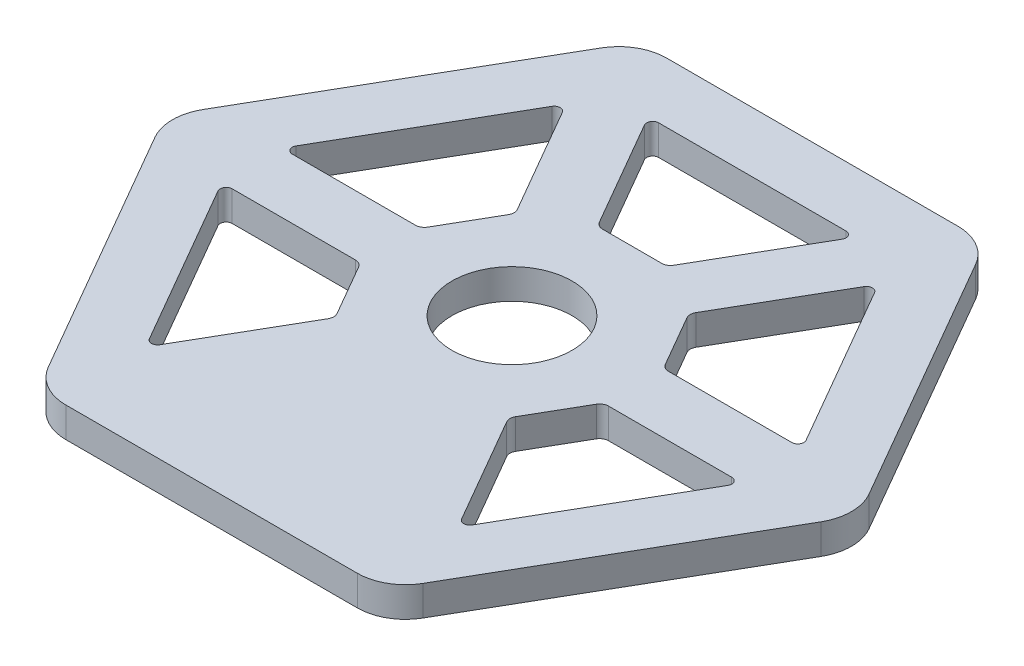
SolidWorks part; units mm, degrees
ref_plane "Front Plane" through (0, 0, 0) normal (0, 0, 1) x (1, 0, 0)
ref_plane "Top Plane" through (0, 0, 0) normal (0, 1, 0) x (1, 0, 0)
ref_plane "Right Plane" through (0, 0, 0) normal (1, 0, 0) x (0, 0, -1)
sketch "Sketch1" plane through (0, 0, 0) normal (0, 1, 0) x (1, 0, 0)
  line L1 (-57.735, 0) -> (-28.8675, -50)
  line L2 (-28.8675, -50) -> (28.8675, -50)
  line L3 (28.8675, -50) -> (57.735, 0)
  line L4 (57.735, 0) -> (28.8675, 50)
  line L5 (28.8675, 50) -> (-28.8675, 50)
  line L6 (-28.8675, 50) -> (-57.735, 0)
  circle A0 centre (0, 0) radius 50 construction
  circle A1 centre (0, 0) radius 50 construction
  dimension "D2" = 100
  dimension "D1" = 100
extrude "Boss-Extrude1" add sketch "Sketch1" along normal blind 5
fillet "Fillet1" radius 8 6 edges at (28.8675, 2.5, -50) (57.735, 2.5, 0) (28.8675, 2.5, 50) (-28.8675, 2.5, 50) (-57.735, 2.5, 0) (-28.8675, 2.5, -50)
sketch "Sketch2" plane through (0, 5, 0) normal (0, 1, 0) x (1, 0, 0)
  line L0 (0, 30) -> (0, 20) construction
  line L1 (0, 40) -> (0, 50) construction
  line L2 (6.2065, 20.75) -> (16.4545, 38.5)
  line L3 (15.5885, 40) -> (-15.5885, 40)
  line L4 (-16.4545, 38.5) -> (-6.2065, 20.75)
  line L5 (24.2487, 50) -> (-24.2487, 50) construction
  line L36 (4.9075, 20) -> (-4.9075, 20)
  line L37 (21.0733, 5) -> (41.5692, 5)
  line L38 (42.4352, 6.5) -> (26.8468, 33.5)
  line L39 (25.1147, 33.5) -> (14.8668, 15.75)
  line L40 (19.7742, 5.75) -> (14.8668, 14.25)
  line L41 (14.8668, -15.75) -> (25.1147, -33.5)
  line L42 (26.8468, -33.5) -> (42.4352, -6.5)
  line L43 (41.5692, -5) -> (21.0733, -5)
  line L44 (14.8668, -14.25) -> (19.7742, -5.75)
  line L45 (-6.2065, -20.75) -> (-16.4545, -38.5) construction
  line L46 (-15.5885, -40) -> (15.5885, -40) construction
  line L47 (16.4545, -38.5) -> (6.2065, -20.75) construction
  line L48 (-4.9075, -20) -> (4.9075, -20) construction
  line L49 (-21.0733, -5) -> (-41.5692, -5)
  line L50 (-42.4352, -6.5) -> (-26.8468, -33.5)
  line L51 (-25.1147, -33.5) -> (-14.8668, -15.75)
  line L52 (-19.7742, -5.75) -> (-14.8668, -14.25)
  line L53 (-14.8668, 15.75) -> (-25.1147, 33.5)
  line L54 (-26.8468, 33.5) -> (-42.4352, 6.5)
  line L55 (-41.5692, 5) -> (-21.0733, 5)
  line L56 (-14.8668, 14.25) -> (-19.7742, 5.75)
  circle A0 centre (0, 0) radius 10
  circle A1 centre (0, 30) radius 10 construction
  arc A3 (-15.5885, 40) -> (-16.4545, 38.5) centre (-15.5885, 39) ccw
  arc A4 (16.4545, 38.5) -> (15.5885, 40) centre (15.5885, 39) ccw
  arc A5 (4.9075, 20) -> (6.2065, 20.75) centre (4.9075, 21.5) ccw
  arc A6 (-4.9075, 20) -> (-6.2065, 20.75) centre (-4.9075, 21.5) cw
  arc A7 (19.7742, 5.75) -> (21.0733, 5) centre (21.0733, 6.5) ccw
  arc A8 (41.5692, 5) -> (42.4352, 6.5) centre (41.5692, 6) ccw
  arc A9 (26.8468, 33.5) -> (25.1147, 33.5) centre (25.9808, 33) ccw
  arc A10 (14.8668, 14.25) -> (14.8668, 15.75) centre (16.1658, 15) cw
  arc A11 (14.8668, -14.25) -> (14.8668, -15.75) centre (16.1658, -15) ccw
  arc A12 (25.1147, -33.5) -> (26.8468, -33.5) centre (25.9808, -33) ccw
  arc A13 (42.4352, -6.5) -> (41.5692, -5) centre (41.5692, -6) ccw
  arc A14 (19.7742, -5.75) -> (21.0733, -5) centre (21.0733, -6.5) cw
  arc A15 (-4.9075, -20) -> (-6.2065, -20.75) centre (-4.9075, -21.5) ccw construction
  arc A16 (-16.4545, -38.5) -> (-15.5885, -40) centre (-15.5885, -39) ccw construction
  arc A17 (15.5885, -40) -> (16.4545, -38.5) centre (15.5885, -39) ccw construction
  arc A18 (4.9075, -20) -> (6.2065, -20.75) centre (4.9075, -21.5) cw construction
  arc A19 (-19.7742, -5.75) -> (-21.0733, -5) centre (-21.0733, -6.5) ccw
  arc A20 (-41.5692, -5) -> (-42.4352, -6.5) centre (-41.5692, -6) ccw
  arc A21 (-26.8468, -33.5) -> (-25.1147, -33.5) centre (-25.9808, -33) ccw
  arc A22 (-14.8668, -14.25) -> (-14.8668, -15.75) centre (-16.1658, -15) cw
  arc A23 (-14.8668, 14.25) -> (-14.8668, 15.75) centre (-16.1658, 15) ccw
  arc A24 (-25.1147, 33.5) -> (-26.8468, 33.5) centre (-25.9808, 33) ccw
  arc A25 (-42.4352, 6.5) -> (-41.5692, 5) centre (-41.5692, 6) ccw
  arc A26 (-19.7742, 5.75) -> (-21.0733, 5) centre (-21.0733, 6.5) cw
  point P19 (0, 20)
  point P30 (0, 0)
  point P66 (0, 0)
  point P88 (0, 0)
  dimension "D1" = 20
  dimension "D3" = 20
  dimension "D6" = 1
  dimension "D8" = 1.5
  dimension "D2" = 30
  dimension "D4" = 10
  dimension "D5" = 10
  dimension "D7" = 20
  dimension "D9" = 6
extrude "Cut-Extrude1" cut sketch "Sketch2" against normal blind 10
